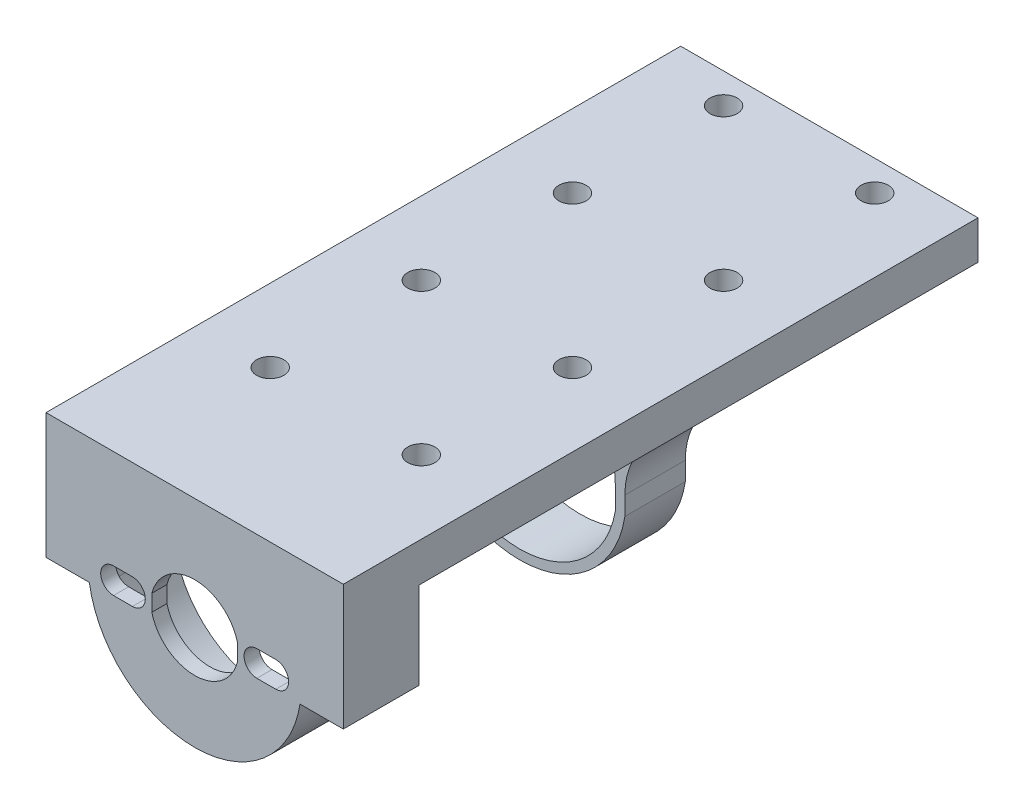
SolidWorks part; units mm, degrees
ref_plane "Front Plane" through (0, 0, 0) normal (0, 0, 1) x (1, 0, 0)
ref_plane "Top Plane" through (0, 0, 0) normal (0, 1, 0) x (1, 0, 0)
ref_plane "Right Plane" through (0, 0, 0) normal (1, 0, 0) x (0, 0, -1)
sketch "Sketch1" plane through (0, 0, 0) normal (0, 0, 1) x (1, 0, 0)
  line L0 (1000, 0) -> (13.9415, 0) construction
  line L1 (0, 0) -> (0, 50000) construction
  line L2 (-13.9415, 0) -> (-19.675, 0)
  line L3 (-12.675, 0) -> (-12.675, -1.8)
  line L4 (-12.675, -1.8) -> (-19.675, -1.8)
  line L5 (-19.675, 0) -> (-19.675, -1.8)
  line L6 (12.675, -1.8) -> (19.675, -1.8)
  line L7 (19.675, 0) -> (19.675, -1.8)
  line L8 (13.9415, 0) -> (19.675, 0)
  line L9 (12.675, 0) -> (12.675, -1.8)
  line L10 (-13.9415, 0) -> (-50000, 0) construction
  line L11 (12.675, 0) -> (-12.675, 0) construction
  arc A0 (-12.675, 0) -> (12.675, 0) centre (0, -2.1649) cw
  arc A1 (-13.9415, 0) -> (13.9415, 0) centre (0, -2.1649) cw
  point P6 (0, 10.6937)
  point P10 (0, 11.9437)
  dimension "D1" = 25.35
  dimension "D3" = 1.25
  dimension "D4" = 1.8
  dimension "D2" = 7
extrude "Boss-Extrude1" add sketch "Sketch1" along normal blind 10
sketch "Sketch4" plane through (0, 0, 0) normal (0, 0, -1) x (-1, 0, 0)
  line L0 (13.9415, 0) -> (20, 0)
  line L1 (-19.675, 0) -> (-13.9415, 0)
  line L2 (-19.675, 0) -> (-19.675, 13)
  line L3 (-19.675, 13) -> (20, 13)
  line L4 (20, 0) -> (20, 13)
  arc A0 (-13.9415, 0) -> (13.9415, 0) centre (0, -4.5015) cw
  dimension "D1" = 13
extrude "Boss-Extrude2" [suppressed] add sketch "Sketch4" against normal up to surface (15 mm away)
sketch "Sketch2" [suppressed] plane through (0, 13, 0) normal (0, 1, 0) x (1, 0, 0)
  line L0 (0, 0) -> (0, 50000) construction
  line L5 (20, -15) -> (-20, -15) construction
  circle A0 centre (-10.5, -7.5) radius 1.5
  circle A1 centre (10.5, -7.5) radius 1.5
  dimension "D1" = 3
  dimension "D3" = 7.5
  dimension "D2" = 10.5
extrude "Cut-Extrude1" [suppressed] cut sketch "Sketch2" against normal blind 7 and the other way through all
mirror "Mirror1" about plane through (-12.675, -1.8, 10) normal (0, 1, 0) of "Cut-Extrude1", "Boss-Extrude1", "Boss-Extrude2"
sketch "Sketch6" plane through (0, 0, 0) normal (0, 0, -1) x (-1, 0, 0)
  line L0 (0.775, 13) -> (-24.649, 13) construction
  line L1 (13.9415, 0) -> (19.675, 0)
  line L2 (-19.675, 0) -> (-13.9415, 0)
  line L3 (-19.675, 0) -> (-19.675, 13)
  line L4 (-19.675, 13) -> (19.675, 13)
  line L5 (19.675, 0) -> (19.675, 13)
  arc A1 (-13.9415, 0) -> (13.9415, 0) centre (0, -2.1649) cw
  arc A2 (13.9415, 0) -> (-13.9415, 0) centre (0, -2.1649) ccw construction
  dimension "D2" = 13
extrude "Boss-Extrude3" add sketch "Sketch6" against normal up to surface (10 mm away) up to face at (0, -1.8, 10)
sketch "Sketch8" plane through (0, 13, 0) normal (0, 1, 0) x (1, 0, 0)
  line L0 (-19.675, -10) -> (-19.675, 0) construction
  line L1 (-19.675, -5) -> (19.675, -5) construction
  line L2 (19.675, -10) -> (19.675, 0) construction
  line L3 (0, 0) -> (0, -10) construction
  line L4 (-19.675, 0) -> (19.675, 0) construction
  line L5 (19.675, -10) -> (-19.675, -10) construction
  circle A0 centre (-10.5, -5) radius 1.25
  circle A1 centre (10.5, -5) radius 1.25
  dimension "D1" = 2.5
  dimension "D2" = 10.5
extrude "Cut-Extrude2" [suppressed] cut sketch "Sketch8" against normal blind 5
sketch "Sketch9" plane through (0, 0, 0) normal (0, 0, -1) x (-1, 0, 0)
  line L0 (0, 10.6937) -> (0, -14.2937) construction
  arc A0 (12.675, 0) -> (-12.675, 0) centre (0, -2.1649) ccw construction
  arc A1 (-12.675, -3.6) -> (12.675, -3.6) centre (0, -1.4351) ccw construction
sketch "Sketch10" plane through (19.675, 0, 0) normal (1, 0, 0) x (0, 0, -1)
  line L1 (-10, 4.7) -> (0, 4.7) construction
  line L2 (-10, -3.6) -> (-10, 13) construction
  line L3 (0, 10.6937) -> (0, -14.2937) construction
  line L4 (-5, 13) -> (-5, -3.6) construction
  line L5 (-10, 13) -> (0, 13) construction
  line L6 (-10, -3.6) -> (0, -3.6) construction
  circle A0 centre (-5, 4.7) radius 2.525
  dimension "D1" = 5.05
extrude "Cut-Extrude3" [suppressed] cut sketch "Sketch10" against normal blind 12
sketch "Sketch13" plane through (0, 13, 0) normal (0, 1, 0) x (1, 0, 0)
  line L0 (-19.675, -5) -> (19.675, -5) construction
  line L1 (-19.675, -10) -> (-19.675, 0) construction
  line L2 (19.675, -10) -> (19.675, 0) construction
  line L3 (0, 0) -> (0, -10) construction
  line L4 (19.675, -10) -> (-19.675, -10) construction
  line L6 (1.5011, -5) -> (0.7506, -3.7)
  line L7 (0.7506, -3.7) -> (-0.7506, -3.7)
  line L8 (-0.7506, -3.7) -> (-1.5011, -5)
  line L9 (-1.5011, -5) -> (-0.7506, -6.3)
  line L10 (-0.7506, -6.3) -> (0.7506, -6.3)
  line L11 (0.7506, -6.3) -> (1.5011, -5)
  circle A0 centre (0, -5) radius 1.3 construction
  point P11 (0, -5)
  dimension "D1" = 2.6
hole_wizard "M2 Clearance Hole1" [suppressed] positions "3DSketch1" profile "Sketch14" hole size "M2" standard "ANSI Metric"
sketch3d "3DSketch1"
  point P0 (0, 13, 5)
sketch "Sketch14" plane through (0, 13, 5) normal (1, 0, 0) x (0, 0, 1)
  line L0 (0, 0) -> (0, 5.2811)
  line L1 (0, 5.2811) -> (1.3, 4.5)
  line L2 (1.3, 4.5) -> (1.3, 0)
  line L5 (1.3, 0) -> (0, 0)
  line L10 (0, 5.2811) -> (-1.3, 4.5) construction
  line L11 (0, -6.35) -> (0, 107.95) construction
  dimension "Hole Dia." = 2.6
  dimension "Hole Depth" = 4.5
  dimension "Drill Angle" = 118
extrude "Cut-Extrude4" [suppressed] cut sketch "Sketch13" against normal blind 1.5
sketch "Sketch15" plane through (0, 0, 0) normal (0, 0, -1) x (-1, 0, 0)
  line L0 (8.0079, 7.8957) -> (19.675, 7.8957)
  line L1 (-19.675, 13) -> (19.675, 13)
  line L2 (-19.675, 13) -> (-19.675, 7.8957)
  line L3 (-19.675, 7.8957) -> (-8.0079, 7.8957)
  line L4 (19.675, 13) -> (19.675, 7.8957)
  line L5 (19.675, 13) -> (19.675, -3.6) construction
  arc A0 (12.675, 0) -> (-12.675, 0) centre (0, -2.1649) ccw construction
  arc A1 (8.0079, 7.8957) -> (-8.0079, 7.8957) centre (0, -2.1649) ccw
  point P10 (19.625, 7.8957)
extrude "Boss-Extrude4" add sketch "Sketch15" along normal blind 74
hole_wizard "M3 Clearance Hole1" positions "Sketch11" profile "Sketch12" hole size "M3" standard "ANSI Metric" end condition through all
sketch "Sketch11" plane through (0, 13, 0) normal (0, 1, 0) x (1, 0, 0)
  line L1 (19.675, -10) -> (-19.675, -10) construction
  line L2 (0, 74) -> (0, -10) construction
  line L3 (-19.675, 74) -> (19.675, 74) construction
  line L5 (-10, 10) -> (10, 10) construction
  point P0 (-10, 10)
  point P4 (10, 10)
  point P23 (0, 10)
  point P24 (0, 0)
  point P25 (0, 0)
  dimension "D1" = 20
  dimension "D2" = 20
  dimension "D3" = 20
sketch "Sketch12" plane through (-10, 13, -10) normal (1, 0, 0) x (0, 0, 1)
  line L0 (0, 0) -> (0, 28.5437)
  line L1 (0, 28.5437) -> (1.8, 28.5437)
  line L2 (1.8, 28.5437) -> (1.8, 0)
  line L5 (1.8, 0) -> (0, 0)
  line L11 (0, -6.35) -> (0, 107.95) construction
  dimension "Thru Hole Dia." = 3.6
  dimension "Thru Hole Depth" = 28.5437
pattern_linear "LPattern1" count 4 spacing 20 along (0, 0, -1) of "M3 Clearance Hole1"
sketch "Sketch16" plane through (0, 0, -74) normal (0, 0, -1) x (-1, 0, 0)
  line L0 (-19.675, -3.6) -> (-19.675, 7.8957) construction
  line L1 (-19.675, -3.6) -> (-19.675, 7.8957)
  line L2 (19.675, 7.8957) -> (19.675, 13) construction
  line L3 (19.675, 7.8957) -> (19.675, -3.6) construction
  line L4 (13.9415, -3.6) -> (19.675, -3.6) construction
  line L5 (-19.675, -3.6) -> (-13.9415, -3.6) construction
  line L6 (-19.675, 13) -> (-19.675, 7.8957) construction
  line L7 (19.675, 13) -> (-19.675, 13) construction
  line L8 (19.675, 7.8957) -> (19.675, 13)
  line L9 (19.675, 7.8957) -> (19.675, -3.6)
  line L10 (13.9415, -3.6) -> (19.675, -3.6)
  line L11 (-19.675, -3.6) -> (-13.9415, -3.6)
  line L12 (-19.675, 13) -> (-19.675, 7.8957)
  line L13 (19.675, 13) -> (-19.675, 13)
  arc A0 (-13.9415, -3.6) -> (13.9415, -3.6) centre (0, -1.4351) ccw construction
  arc A1 (-13.9415, -3.6) -> (13.9415, -3.6) centre (0, -1.4351) ccw
extrude "Boss-Extrude5" [suppressed] add sketch "Sketch16" along normal blind 2
ref_plane "Plane1" through (0, 0, -33) normal (0, 0, -1) x (-1, 0, 0)
sketch "Sketch17" plane through (0, 0, 10) normal (0, 0, 1) x (1, 0, 0)
  line L0 (12.675, 0) -> (12.675, -3.6) construction
  line L1 (-12.675, -3.6) -> (-12.675, 0) construction
  line L2 (12.675, 0) -> (12.675, -3.6)
  line L3 (-12.675, -3.6) -> (-12.675, 0)
  line L4 (5.675, -0.7099) -> (5.675, -2.8901)
  line L5 (-5.675, -2.8901) -> (-5.675, -0.7099)
  line L6 (-18.1484, -1.8) -> (14.0134, -1.8) construction
  line L7 (-10.7373, -1.8) -> (-8.2373, -1.8) construction
  line L8 (-10.7373, -0.1) -> (-8.2373, -0.1)
  line L9 (-10.7373, -3.5) -> (-8.2373, -3.5)
  line L10 (0, 10.6937) -> (0, -14.2937) construction
  line L11 (10.7373, -1.8) -> (8.2373, -1.8) construction
  line L12 (10.7373, -0.1) -> (8.2373, -0.1)
  line L13 (10.7373, -3.5) -> (8.2373, -3.5)
  arc A0 (-12.675, -3.6) -> (12.675, -3.6) centre (0, -1.4351) ccw construction
  arc A1 (12.675, 0) -> (-12.675, 0) centre (0, -2.1649) ccw construction
  arc A2 (-12.675, -3.6) -> (12.675, -3.6) centre (0, -1.4351) ccw
  arc A3 (12.675, 0) -> (-12.675, 0) centre (0, -2.1649) ccw
  arc A4 (-5.675, -2.8901) -> (5.675, -2.8901) centre (0, -1.4351) ccw
  arc A5 (5.675, -0.7099) -> (-5.675, -0.7099) centre (0, -2.1649) ccw
  arc A6 (-10.7373, -0.1) -> (-10.7373, -3.5) centre (-10.7373, -1.8) ccw
  arc A7 (-8.2373, -3.5) -> (-8.2373, -0.1) centre (-8.2373, -1.8) ccw
  arc A8 (10.7373, -0.1) -> (10.7373, -3.5) centre (10.7373, -1.8) cw
  arc A9 (8.2373, -3.5) -> (8.2373, -0.1) centre (8.2373, -1.8) cw
  point P14 (-9.4873, -1.8)
  point P16 (-5.675, -1.8)
  point P26 (9.4873, -1.8)
  dimension "D3" = 1.7
  dimension "D2" = 2.5
  dimension "D1" = 7
extrude "Boss-Extrude6" add sketch "Sketch17" against normal blind 2
sketch "Sketch18" plane through (0, 0, -33) normal (0, 0, -1) x (-1, 0, 0)
  line L0 (12.675, -3.6) -> (12.675, 0) construction
  line L1 (-12.675, 0) -> (-12.675, -3.6) construction
  line L2 (12.675, -3.6) -> (12.675, 0)
  line L3 (-12.675, 0) -> (-12.675, -3.6)
  line L4 (-12.675, 0) -> (-12.675, 7.8957)
  line L5 (-19.675, 7.8957) -> (-8.0079, 7.8957) construction
  line L6 (12.675, 0) -> (12.675, 7.8957)
  line L7 (8.0079, 7.8957) -> (19.675, 7.8957) construction
  line L8 (-13.9415, -3.6) -> (-13.9415, 7.8957)
  line L9 (13.9415, -3.6) -> (13.8415, 7.8957)
  line L10 (13.8415, 7.8957) -> (12.675, 7.8957)
  line L11 (-13.9415, 7.8957) -> (-12.675, 7.8957)
  arc A0 (-12.675, -3.6) -> (12.675, -3.6) centre (0, -1.4351) ccw construction
  arc A1 (-12.675, -3.6) -> (12.675, -3.6) centre (0, -1.4351) ccw
  arc A2 (-13.9415, -3.6) -> (13.9415, -3.6) centre (0, -1.4351) ccw construction
  arc A3 (-13.9415, -3.6) -> (13.9415, -3.6) centre (0, -1.4351) ccw
extrude "Boss-Extrude7" add sketch "Sketch18" along normal blind 8
fillet "Fillet1" radius 10 4 edges at (12.675, 7.8957, -37) (-12.675, 7.8957, -37) (13.9415, 7.8957, -37) (-13.8415, 7.8957, -37)
equation "\"ArcLength\"=25.35"
equation "\"D1@Sketch1\"=\"ArcLength\""
equation "\"ArcThickness\"=1.25"
equation "\"D3@Sketch1\"=\"ArcThickness\""
equation "\"BracketLength\"=7"
equation "\"BracketThicknes\"=1.8"
equation "\"D4@Sketch1\"=\"BracketThicknes\""
equation "\"D2@Sketch1\"=\"BracketLength\""
equation "\"MatingHardware\"=3"
equation "\"D1@Sketch2\"=\"MatingHardware\""
equation "\"BracketDepth\"=10"
equation "\"D1@Boss-Extrude1\"=\"BracketDepth\""
